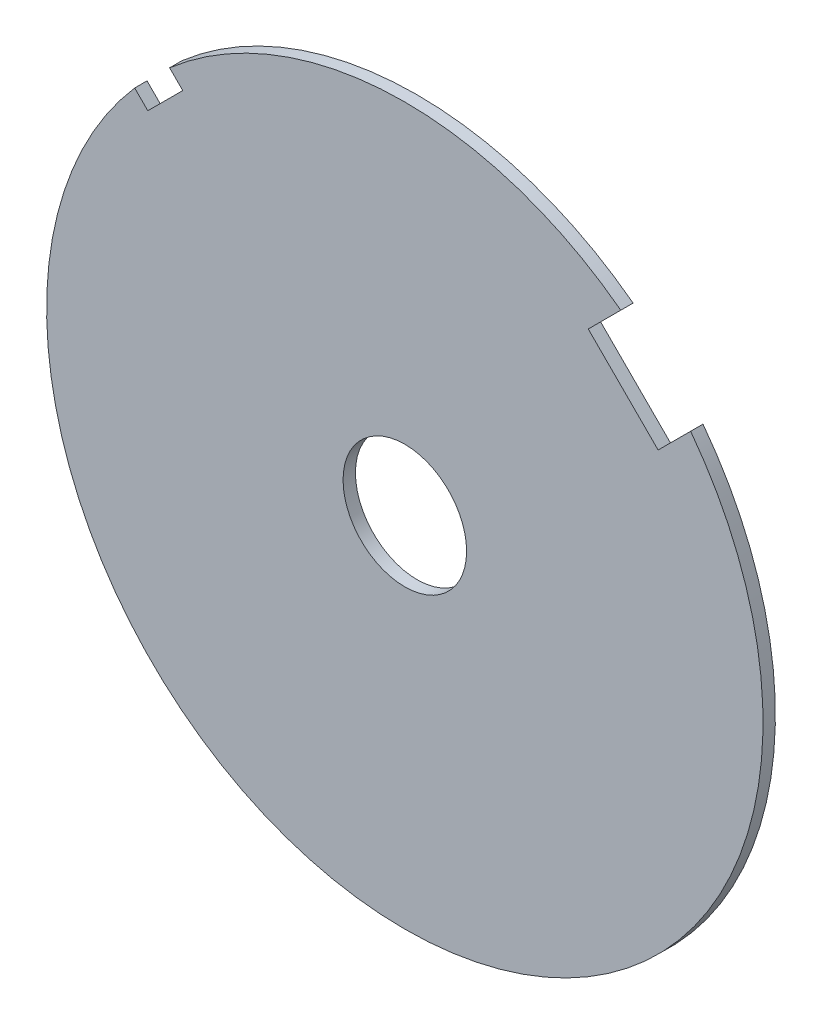
SolidWorks part; units mm, degrees
ref_plane "Alzado" through (0, 0, 0) normal (0, 0, 1) x (1, 0, 0)
ref_plane "Planta" through (0, 0, 0) normal (0, 1, 0) x (1, 0, 0)
ref_plane "Vista lateral" through (0, 0, 0) normal (1, 0, 0) x (0, 0, -1)
sketch "Croquis1" plane through (0, 0, 0) normal (0, 0, 1) x (1, 0, 0)
  circle A0 centre (0, 0) radius 7.25
  dimension "D1" = 14.5
sheet metal parameters "Chapa metálica1" thickness 0.25 parameters "D1"=0.7366, "Espesor"=0.25
base flange "Brida base1" sketch "Croquis1" thickness 0.25 reverse thickness direction no parameters "D1"=0.7366
sketch "Croquis5" plane through (0, 0, -0.25) normal (0, 0, -1) x (-1, 0, 0)
  circle A0 centre (0, 0) radius 1.25
  dimension "D1" = 2.5
extrude "Cortar-Extruir1" cut sketch "Croquis5" against normal blind 10 normal cut yes
sketch "Croquis6" plane through (0, 0, 0) normal (0, 0, 1) x (1, 0, 0)
  line L0 (0, 0) -> (-7.1594, 7.1594) construction
  line L1 (0, 0) -> (6.852, 6.852) construction
  line L2 (0, 0) -> (0, 5.873) construction
  line L4 (-5.4801, 4.773) -> (-4.773, 5.4801)
  line L5 (-5.4801, 4.773) -> (-5.202, 4.4949)
  line L6 (-5.202, 4.4949) -> (-4.4949, 5.202)
  line L7 (-4.773, 5.4801) -> (-4.4949, 5.202)
  line L8 (5.8336, 4.4194) -> (4.4194, 5.8336)
  line L9 (5.8336, 4.4194) -> (5.1265, 3.7123)
  line L10 (5.1265, 3.7123) -> (3.7123, 5.1265)
  line L11 (4.4194, 5.8336) -> (3.7123, 5.1265)
  circle A0 centre (0, 0) radius 7.25 construction
  circle A2 centre (0, 0) radius 6.875 construction
  point P13 (-4.8485, 4.8485)
  point P14 (4.4194, 4.4194)
  point P15 (5.1265, 5.1265)
  point P18 (-5.1265, 5.1265)
  dimension "D7" = 13.75
  dimension "D1" = 45
  dimension "D2" = 45
  dimension "D3" = 1
  dimension "D5" = 1
  dimension "D6" = 2
extrude "Cortar-Extruir2" cut sketch "Croquis6" against normal blind 10 normal cut yes
flat pattern "Chapa desplegada1" [suppressed]
sketch "Líneas de pliegue1" plane through (0, 0, 0) normal (0, 1, 0) x (-1, 0, 0)
